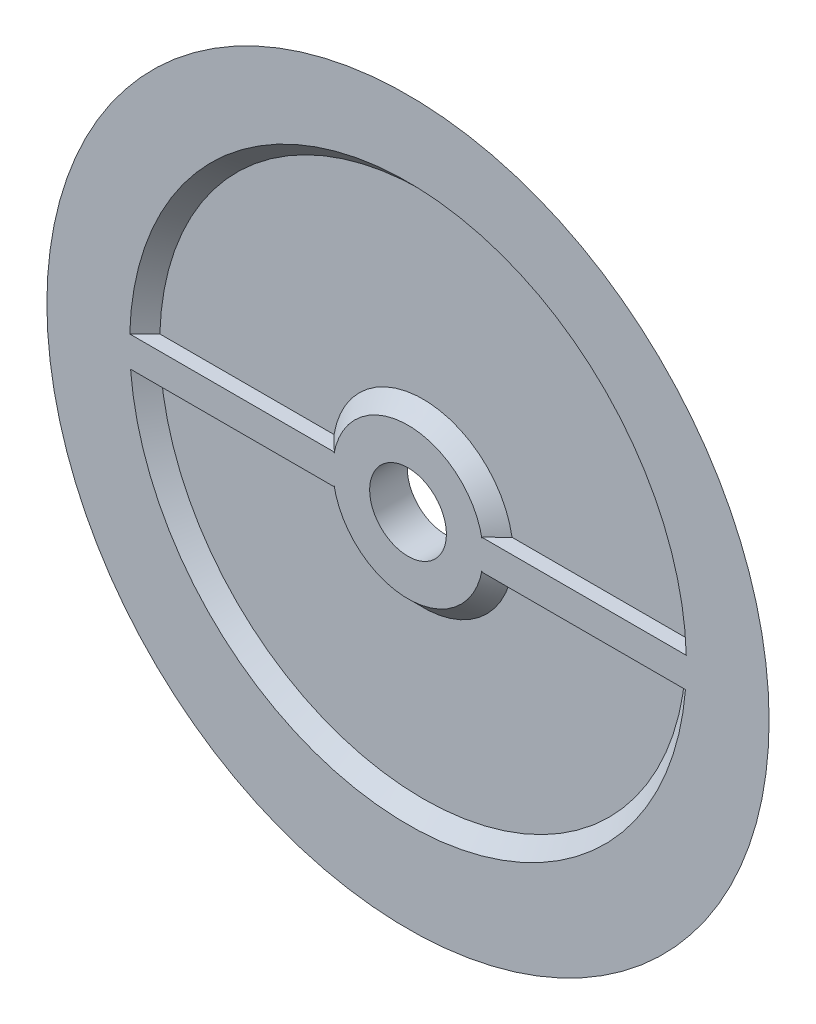
SolidWorks part; units mm, degrees
ref_plane "정면" through (0, 0, 0) normal (0, 0, 1) x (1, 0, 0)
ref_plane "윗면" through (0, 0, 0) normal (0, 1, 0) x (1, 0, 0)
ref_plane "우측면" through (0, 0, 0) normal (1, 0, 0) x (0, 0, -1)
sketch "스케치1" plane through (0, 0, 0) normal (0, 0, 1) x (1, 0, 0)
  circle A0 centre (0, 0) radius 37
  dimension "D1" = 74
extrude "보스-돌출1" add sketch "스케치1" along normal blind 5
ref_plane "평면1" through (0, 0, 2.5) normal (0, 0, 1) x (1, 0, 0)
sketch "스케치3" plane through (0, 0, 0) normal (0, 1, 0) x (1, 0, 0)
  line L0 (-37, -5) -> (-37, 0)
  line L1 (-37, 0) -> (-48, -5)
  line L2 (-48, -5) -> (-37, -5)
  line L3 (0, 6.4626) -> (0, -29.948) construction
  dimension "D1" = 11
revolve "회전1" add sketch "스케치3" angle 360 about L3
sketch "스케치4" plane through (0, 0, 0) normal (0, 0, -1) x (-1, 0, 0)
  circle A0 centre (0, 0) radius 34.4
  circle A1 centre (0, 0) radius 30.4
  circle A2 centre (0, 0) radius 37 construction
  dimension "D1" = 4
  dimension "D2" = 2.6
extrude "보스-돌출2" add sketch "스케치4" along normal blind 0.8
sketch "스케치5" plane through (0, 0, 0) normal (0, 0, -1) x (-1, 0, 0)
  circle A0 centre (0, 0) radius 5.1
  dimension "D1" = 10.2
extrude "컷-돌출1" cut sketch "스케치5" against normal through all contours A0
sketch "스케치6" plane through (0, 0, 5) normal (0, 0, 1) x (1, 0, 0)
  circle A0 centre (0, 0) radius 10
  circle A1 centre (0, 0.9905) radius 37
  dimension "D1" = 74
  dimension "D2" = 20
extrude "컷-돌출2" cut sketch "스케치6" against normal blind 2 draft 45
sketch "스케치7" plane through (0, 0, 5) normal (0, 0, 1) x (1, 0, 0)
  line L1 (-40.1871, 2) -> (-14.8661, 2)
  line L2 (-40.1871, 2) -> (-40.1871, -2)
  line L3 (-40.1871, -2) -> (-14.8661, -2)
  line L4 (-14.8661, 2) -> (-14.8661, -2)
  line L5 (-40.1871, 2) -> (-14.8661, -2) construction
  line L6 (-40.1871, -2) -> (-14.8661, 2) construction
  circle A1 centre (0, 0) radius 15 construction
  point P0 (-27.5266, 0)
  dimension "D1" = 4
extrude "보스-돌출3" add sketch "스케치7" against normal blind 2
sketch "스케치9" plane through (-14.8661, 0, 0) normal (1, 0, 0) x (0, 0, -1)
  line L1 (-5, 2) -> (-3, 2)
  line L2 (-5, 2) -> (-5, -2)
  line L3 (-5, -2) -> (-3, -2)
  line L4 (-3, 2) -> (-3, -2)
extrude "보스-돌출5" add sketch "스케치9" along normal blind 5
sketch "스케치10" plane through (0, 0, 0) normal (1, 0, 0) x (0, 0, -1)
  line L0 (37.3425, 0) -> (-26.3325, 0) construction
pattern_circular "원형 패턴1" count 2 over 360 about axis through (0, 0, -37.3425) along (0, 0, 1) of "보스-돌출3", "보스-돌출5"
